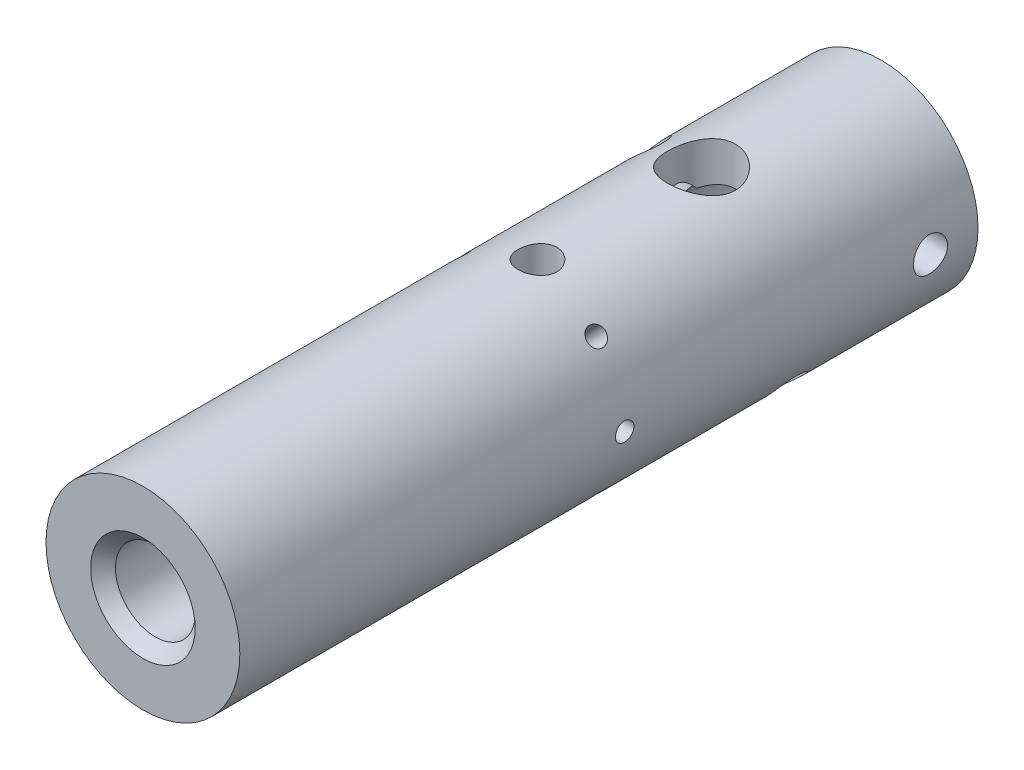
SolidWorks part; units mm, degrees
material "6061-T6 (SS)"
ref_plane "Front Plane" through (0, 0, 0) normal (0, 0, 1) x (1, 0, 0)
ref_plane "Top Plane" through (0, 0, 0) normal (0, 1, 0) x (1, 0, 0)
ref_plane "Right Plane" through (0, 0, 0) normal (1, 0, 0) x (0, 0, -1)
sketch "Sketch1" plane through (0, 0, 0) normal (0, 0, 1) x (1, 0, 0)
  circle A0 centre (0, 0) radius 7.9375
  dimension "D1" = 15.875
extrude "Extrude1" add sketch "Sketch1" along normal mid plane 60.452
sketch "Sketch28" plane through (0, 0, -30.226) normal (0, 0, -1) x (-1, 0, 0)
  line L0 (0, 0) -> (0, 7.9375) construction
  line L1 (0, 0) -> (7.9375, 0) construction
  line L2 (0, 0) -> (5.6127, 5.6127) construction
  circle A0 centre (0, 0) radius 7.9375 construction
hole_wizard "5/16-18 Tapped Hole1" positions "3DSketch1" profile "Sketch2" tap size "5/16-18" standard "Ansi Inch"
sketch3d "3DSketch1"
  line L0 (0, 0, 30.226) -> (0, 0, -30.226) construction
  point P0 (0, 0, 30.226)
sketch "Sketch2" plane through (0, 0, 30.226) normal (1, 0, 0) x (0, -1, 0)
  line L0 (0, 0) -> (0, 27.3611)
  line L1 (0, 27.3611) -> (3.2639, 25.4)
  line L2 (3.2639, 25.4) -> (3.2639, 0)
  line L5 (3.2639, 0) -> (0, 0)
  line L10 (0, 27.3611) -> (-3.2639, 25.4) construction
  line L11 (0, -6.35) -> (0, 107.95) construction
  dimension "Tap Drill Dia." = 6.5278
  dimension "Tap Drill Depth" = 25.4
  dimension "Drill Angle" = 118
chamfer "Chamfer1" distance 1.016 angle 45 1 edges at (3.2639, 0, 30.226)
sketch "Sketch4" plane through (0, 0, -30.226) normal (0, 0, -1) x (-1, 0, 0)
  point P0 (0, 0)
hole_wizard "3/8 (0.375) Diameter Hole1" positions "Sketch8" profile "Sketch7" hole size "3/8" standard "Ansi Inch"
sketch "Sketch8" plane through (0, 0, -30.226) normal (0, 0, -1) x (-1, 0, 0)
  point P1 (0, 0)
sketch "Sketch7" plane through (0, 0, -30.226) normal (1, 0, 0) x (0, 1, 0)
  line L0 (0, 0) -> (0, 39.6916)
  line L1 (0, 39.6916) -> (4.7625, 36.83)
  line L2 (4.7625, 36.83) -> (4.7625, 0)
  line L5 (4.7625, 0) -> (0, 0)
  line L10 (0, 39.6916) -> (-4.7625, 36.83) construction
  line L11 (0, -6.35) -> (0, 107.95) construction
  dimension "Hole Dia." = 9.525
  dimension "Hole Depth" = 36.83
  dimension "Drill Angle" = 118
ref_plane "Plane1" through (7.9375, 0, 0) normal (1, 0, 0) x (0, 0, -1)
sketch "Sketch9" plane through (7.9375, 0, 0) normal (1, 0, 0) x (0, 0, -1)
  line L0 (30.226, 0) -> (26.3398, 0) construction
  line L1 (30.226, -7.9375) -> (30.226, 7.9375) construction
  line L2 (8.7312, 0) -> (-8.7312, 0) construction
  line L3 (26.3398, 0) -> (16.6878, 0) construction
  line L4 (16.6878, 0) -> (15.5194, 0) construction
  line L5 (15.5194, 0) -> (2.0828, 0) construction
  line L6 (2.0828, 0) -> (1.2954, 0) construction
  dimension "D1" = 3.8862
  dimension "D2" = 13.5382
  dimension "D3" = 14.7066
  dimension "D4" = 28.1432
  dimension "D5" = 28.9306
hole_wizard "#35 (0.11) Diameter Hole4" positions "Sketch18" profile "Sketch17" hole size "#35" standard "Ansi Inch" end condition through all
sketch "Sketch18" plane through (7.9375, 0, 0) normal (1, 0, 0) x (0, 0, -1)
  point P1 (26.3398, 0)
sketch "Sketch17" plane through (7.9375, 0, -26.3398) normal (0, 1, 0) x (0, 0, -1)
  line L0 (0, 0) -> (0, 15.875)
  line L1 (0, 15.875) -> (1.397, 15.875)
  line L2 (1.397, 15.875) -> (1.397, 0)
  line L5 (1.397, 0) -> (0, 0)
  line L11 (0, -6.35) -> (0, 107.95) construction
  dimension "Thru Hole Dia." = 2.794
  dimension "Thru Hole Depth" = 15.875
hole_wizard "#53 (0.0595) Diameter Hole1" positions "Sketch21" profile "Sketch22" hole size "#53" standard "Ansi Inch" end condition through all
sketch "Sketch21" plane through (7.9375, 0, 0) normal (1, 0, 0) x (0, 0, -1)
  point P4 (1.2954, 0)
sketch "Sketch22" plane through (7.9375, 0, -1.2954) normal (0, 1, 0) x (0, 0, -1)
  line L0 (0, 0) -> (0, 19.1628)
  line L1 (0, 19.1628) -> (0.7556, 19.1628)
  line L2 (0.7556, 19.1628) -> (0.7556, 0)
  line L5 (0.7556, 0) -> (0, 0)
  line L11 (0, -6.35) -> (0, 107.95) construction
  dimension "Thru Hole Dia." = 1.5113
  dimension "Thru Hole Depth" = 19.1628
pattern_circular "CirPattern1" count 4 every 45 about axis through (0, 0, 30.226) along (0, 0, -1) of "#53 (0.0595) Diameter Hole1"
ref_plane "Plane3" through (0, 7.9375, -30.226) normal (0, 1, 0) x (-1, 0, 0)
sketch "Sketch29" plane through (0, 7.9375, -30.226) normal (0, 1, 0) x (-1, 0, 0)
  line L0 (0, 0) -> (0, 14.7066) construction
  line L1 (0, 0) -> (0, 28.1432) construction
  line L2 (0, 60.452) -> (0, 0) construction
  dimension "D1" = 14.7066
  dimension "D2" = 28.1432
hole_wizard "7/32 (0.21875) Diameter Hole1" positions "Sketch32" profile "Sketch31" hole size "7/32" standard "Ansi Inch"
sketch "Sketch32" plane through (0, 7.9375, -30.226) normal (0, 1, 0) x (-1, 0, 0)
  point P1 (0, 14.7066)
sketch "Sketch31" plane through (0, 7.9375, -15.5194) normal (1, 0, 0) x (0, 0, 1)
  line L0 (0, 0) -> (0, 17.6713)
  line L1 (0, 17.6713) -> (2.7781, 16.002)
  line L2 (2.7781, 16.002) -> (2.7781, 0)
  line L5 (2.7781, 0) -> (0, 0)
  line L10 (0, 17.6713) -> (-2.7781, 16.002) construction
  line L11 (0, -6.35) -> (0, 107.95) construction
  dimension "Hole Dia." = 5.5562
  dimension "Hole Depth" = 16.002
  dimension "Drill Angle" = 118
ref_plane "Plane4" through (-5.6127, 5.6127, -30.226) normal (-0.7071, 0.7071, 0) x (-0.7071, -0.7071, 0)
sketch "Sketch33" plane through (-5.6127, 5.6127, -30.226) normal (-0.7071, 0.7071, 0) x (-0.7071, -0.7071, 0)
  line L0 (0, 0) -> (0, 13.5382) construction
  dimension "D1" = 13.5382
hole_wizard "1/8 (0.125) Diameter Hole8" positions "Sketch35" profile "Sketch34" hole size "1/8" standard "Ansi Inch" end condition through all
sketch "Sketch35" plane through (-5.6127, 5.6127, -30.226) normal (-0.7071, 0.7071, 0) x (-0.7071, -0.7071, 0)
  point P1 (0, 13.5382)
sketch "Sketch34" plane through (-5.6127, 5.6127, -16.6878) normal (0, 0, 1) x (-0.7071, -0.7071, 0)
  line L0 (0, 0) -> (0, 19.1628)
  line L1 (0, 19.1628) -> (1.5875, 19.1628)
  line L2 (1.5875, 19.1628) -> (1.5875, 0)
  line L5 (1.5875, 0) -> (0, 0)
  line L11 (0, -6.35) -> (0, 107.95) construction
  dimension "Thru Hole Dia." = 3.175
  dimension "Thru Hole Depth" = 19.1628
hole_wizard "1/8 (0.125) Diameter Hole9" positions "Sketch38" profile "Sketch37" hole size "1/8" standard "Ansi Inch"
sketch "Sketch38" plane through (0, 7.9375, -30.226) normal (0, 1, 0) x (-1, 0, 0)
  point P1 (0, 28.1432)
sketch "Sketch37" plane through (0, 7.9375, -2.0828) normal (1, 0, 0) x (0, 0, 1)
  line L0 (0, 0) -> (0, 16.9559)
  line L1 (0, 16.9559) -> (1.5875, 16.002)
  line L2 (1.5875, 16.002) -> (1.5875, 0)
  line L5 (1.5875, 0) -> (0, 0)
  line L10 (0, 16.9559) -> (-1.5875, 16.002) construction
  line L11 (0, -6.35) -> (0, 107.95) construction
  dimension "Hole Dia." = 3.175
  dimension "Hole Depth" = 16.002
  dimension "Drill Angle" = 118
